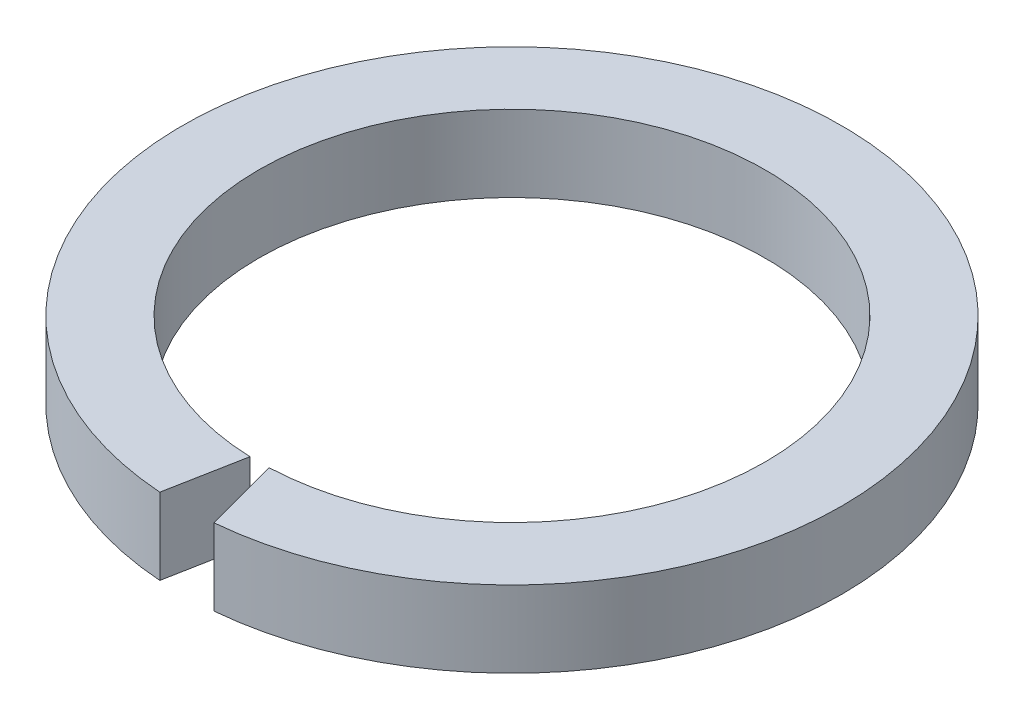
SolidWorks part; units mm, degrees
ref_plane "Front Plane" through (0, 0, 0) normal (0, 0, 1) x (1, 0, 0)
ref_plane "Top Plane" through (0, 0, 0) normal (0, 1, 0) x (1, 0, 0)
ref_plane "Right Plane" through (0, 0, 0) normal (1, 0, 0) x (0, 0, -1)
sketch "Sketch1" plane through (0, 0, 0) normal (0, 1, 0) x (1, 0, 0)
  circle A0 centre (0, 0) radius 16.55
  circle A1 centre (0, 0) radius 21.55
extrude "Boss-Extrude1" add sketch "Sketch1" along normal blind 5
sketch "Sketch3" plane through (0, 0, 0) normal (0, 1, 0) x (1, 0, 0)
  line L0 (0, 0) -> (0, -27.1481) construction
  line L1 (-1.7584, -22.6892) -> (2.3055, -22.6892)
  line L2 (0, -15.9931) -> (-0.4889, -15.9931)
  line L3 (0, -15.9931) -> (0.5048, -15.9931)
  line L4 (0.5048, -15.9931) -> (2.3055, -22.6892)
  line L5 (-1.7584, -22.6892) -> (-0.4889, -15.9931)
  point P7 (0, -13.4195)
extrude "Cut-Extrude2" cut sketch "Sketch3" against normal blind 12 and the other way blind 15
